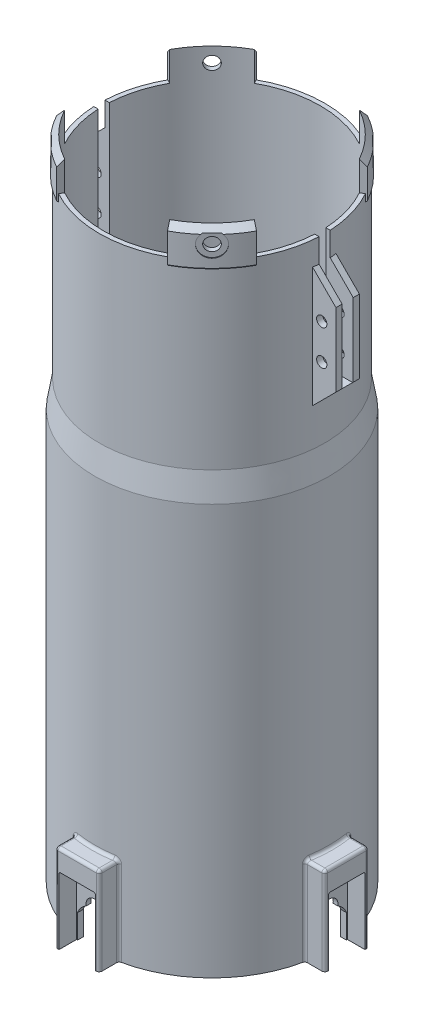
SolidWorks part; units mm, degrees
ref_plane "Front Plane" through (0, 0, 0) normal (0, 0, 1) x (1, 0, 0)
ref_plane "Top Plane" through (0, 0, 0) normal (0, 1, 0) x (1, 0, 0)
ref_plane "Right Plane" through (0, 0, 0) normal (1, 0, 0) x (0, 0, -1)
sketch "Sketch1" plane through (0, 0, 0) normal (0, 1, 0) x (1, 0, 0)
  circle A0 centre (0, 0) radius 40
  circle A1 centre (0, 0) radius 38.5
  dimension "D1" = 80
  dimension "D2" = 1.5
extrude "Boss-Extrude1" add sketch "Sketch1" along normal blind 40
ref_plane "Plane1" through (0, 0, 40) normal (0, 0, 1) x (1, 0, 0)
sketch "Sketch2" plane through (0, 0, 40) normal (0, 0, 1) x (1, 0, 0)
  line L0 (0, 0) -> (0, 45.4693) construction
  line L1 (-40, 0) -> (40, 0) construction
  line L2 (-7.5, 30) -> (7.5, 30)
  line L3 (-7.5, 30) -> (-7.5, 0)
  line L4 (-7.5, 0) -> (7.5, 0)
  line L5 (7.5, 30) -> (7.5, 0)
  line L6 (-7.5, 30) -> (7.5, 0) construction
  line L7 (-7.5, 0) -> (7.5, 30) construction
  point P3 (0, 15)
  dimension "D1" = 15
  dimension "D2" = 30
extrude "Boss-Extrude2" add sketch "Sketch2" along normal blind 6 and the other way up to surface other way up to face at (0, 40, 40)
sketch "Sketch3" plane through (0, 0, 40) normal (0, 0, 1) x (1, 0, 0)
  line L0 (5.8884, 8.095) -> (5.8491, -0.1406)
  line L1 (-5.8884, 8.095) -> (-5.8491, -0.1406)
  line L2 (-5.8491, -0.1406) -> (5.8491, -0.1406)
  arc A18 (-2.9509, 11.5095) -> (-5.8884, 8.095) centre (0, 6) ccw
  arc A19 (2.9509, 11.5095) -> (-2.9509, 11.5095) centre (0, 12.05) ccw
  arc A20 (5.8884, 8.095) -> (2.9509, 11.5095) centre (0, 6) ccw
extrude "Cut-Extrude1" cut sketch "Sketch3" against normal blind 2
sketch "Sketch4" plane through (0, 0, 40) normal (0, 0, 1) x (1, 0, 0)
  line L45 (-5.7, -0.45) -> (5.7, -0.45)
  line L48 (6.2, 0.05) -> (6.2, 22.45)
  line L49 (5.7, 22.95) -> (-5.7, 22.95)
  line L50 (-6.2, 22.45) -> (-6.2, 0.05)
  arc A46 (-6.2, 0.05) -> (-5.7, -0.45) centre (-5.7, 0.05) ccw
  arc A47 (5.7, -0.45) -> (6.2, 0.05) centre (5.7, 0.05) ccw
  arc A48 (6.2, 22.45) -> (5.7, 22.95) centre (5.7, 22.45) ccw
  arc A49 (-5.7, 22.95) -> (-6.2, 22.45) centre (-5.7, 22.45) ccw
extrude "Cut-Extrude2" cut sketch "Sketch4" along normal through all
ref_plane "Plane2" through (0, 0, 41.5) normal (0, 0, 1) x (1, 0, 0)
sketch "Sketch5" plane through (0, 0, 41.5) normal (0, 0, 1) x (1, 0, 0)
  line L66 (-0.3, 25.966) -> (0.3, 25.966)
  line L75 (-5.7, 22.85) -> (-6.2, 22.85)
  line L76 (5.7, 22.85) -> (-5.7, 22.85)
  line L77 (6.2, 22.85) -> (5.7, 22.85)
  line L78 (6.2, 27.05) -> (6.2, 22.85)
  line L79 (0.8, 27.55) -> (5.7, 27.55)
  line L80 (0.3, 25.966) -> (0.3, 27.05)
  line L81 (-0.3, 27.05) -> (-0.3, 25.966)
  line L82 (-5.7, 27.55) -> (-0.8, 27.55)
  line L83 (-6.2, 22.85) -> (-6.2, 27.05)
  arc A42 (6.2, 27.05) -> (5.7, 27.55) centre (5.7, 27.05) ccw
  arc A43 (0.8, 27.55) -> (0.3, 27.05) centre (0.8, 27.05) ccw
  arc A44 (-0.3, 27.05) -> (-0.8, 27.55) centre (-0.8, 27.05) ccw
  arc A45 (-5.7, 27.55) -> (-6.2, 27.05) centre (-5.7, 27.05) ccw
extrude "Cut-Extrude3" cut sketch "Sketch5" along normal blind 3.1
fillet "Fillet1" radius 1 8 edges at (0, 30, 40) (7.5, 30, 42.6453) (7.5, 15, 46) (7.5, 15, 39.2906) (-7.5, 15, 39.2906) (-7.5, 30, 42.6453) (-7.5, 15, 46) (0, 30, 46)
pattern_circular "CirPattern1" count 4 over 360 about axis through (0, 40, 0) along (0, -1, 0) of "Boss-Extrude2", "Cut-Extrude1", "Cut-Extrude2", "Cut-Extrude3", "Fillet1"
sketch "Sketch6" plane through (0, 40, 0) normal (0, 1, 0) x (1, 0, 0)
  circle A0 centre (0, 0) radius 38.5 construction
  circle A1 centre (0, 0) radius 40
  circle A2 centre (0, 0) radius 40
  circle A3 centre (0, 0) radius 38.5
  dimension "D1" = 0
extrude "Boss-Extrude4" add sketch "Sketch6" along normal blind 100
ref_plane "Plane3" through (0, 140, 0) normal (0, 1, 0) x (1, 0, 0)
sketch "Sketch7" plane through (0, 0, 0) normal (0, 0, 1) x (1, 0, 0)
  line L0 (-38.5, 140) -> (-35.194, 160)
  line L1 (38.5, 140) -> (-38.5, 140) construction
  line L2 (-35.194, 160) -> (-37, 160)
  line L3 (-37, 160) -> (-37, 211)
  line L4 (-37, 211) -> (-38.5, 211)
  line L5 (-38.5, 211) -> (-38.5, 149.0744)
  line L6 (0, 140) -> (0, 217.9928) construction
  line L7 (-40, 140) -> (-38.5, 149.0744)
  line L8 (40, 140) -> (-40, 140) construction
  line L9 (-38.5, 140) -> (-40, 140)
  line L10 (40, 140) -> (-40, 140) construction
  point P19 (-36.097, 160)
  dimension "D1" = 1.5
  dimension "D2" = 37
  dimension "D3" = 1.806
  dimension "D4" = 38.5
  dimension "D5" = 1.5
  dimension "D6" = 51
  dimension "D7" = 20
revolve "Revolve1" add sketch "Sketch7" angle 360 about L6
sketch "Sketch8" plane through (0, 0, 0) normal (0, 0, 1) x (1, 0, 0)
  line L0 (-46.3008, 182.5) -> (46.3008, 182.5) construction
  line L2 (-46.3008, 195) -> (-37.5, 203.8008)
  line L3 (-37.5, 211) -> (-37.5, 149.0744)
  line L4 (-37.5, 203.8008) -> (-37.5, 161.1992)
  line L5 (-46.3008, 170) -> (-37.5, 161.1992)
  line L7 (-46.3008, 195) -> (-46.3008, 170)
  circle A0 centre (-41.45, 188.5) radius 1.75
  circle A1 centre (-41.45, 176.5) radius 1.75
  dimension "D2" = 3.5
  dimension "D3" = 3.5
  dimension "D1" = 1
extrude "Boss-Extrude5" add sketch "Sketch8" along normal mid plane 8
sketch "Sketch9" plane through (0, 0, 0) normal (1, 0, 0) x (0, 0, -1)
  line L0 (0, 168.0759) -> (0, 211) construction
  line L1 (38.5, 211) -> (-38.5, 211) construction
  line L7 (-1.9, 195) -> (-1.9, 211)
  line L8 (1.9, 169.8) -> (1.9, 195)
  line L9 (1.9, 169.8) -> (-1.9, 169.8)
  line L10 (-1.9, 169.8) -> (-1.9, 195)
  line L11 (1.9, 195) -> (1.9, 211)
  line L12 (-1.9, 211) -> (1.9, 211)
  point P8 (0, 169.8)
extrude "Cut-Extrude4" cut sketch "Sketch9" against normal through all
mirror "Mirror1" about plane through (0, 0, 0) normal (1, 0, 0) of "Cut-Extrude4", "Boss-Extrude5"
ref_plane "Plane4" through (0, 0, 0) normal (-0.7071, 0, 0.7071) x (0, -1, 0)
sketch "Sketch11" plane through (0, 0, 0) normal (-0.7071, 0, 0.7071) x (0, -1, 0)
  line L0 (-211, 37) -> (-219, 37)
  line L1 (-160, 37) -> (-211, 37) construction
  line L2 (-211, 37) -> (-211, -24.7849) construction
  line L4 (-208.5, 38.5) -> (-211, 38.5)
  line L5 (-219, 39) -> (-209, 39)
  line L6 (-209, 39) -> (-208.5, 38.5)
  line L7 (-149.0744, 38.5) -> (-211, 38.5) construction
  line L8 (-211, 38.5) -> (-211, -25.8469) construction
  line L9 (-211, 38.5) -> (-211, 37)
  line L10 (-219, 37) -> (-221, 37)
  line L11 (-221, 37) -> (-219, 39)
  dimension "D1" = 2
  dimension "D3" = 45
  dimension "D4" = 10
  dimension "D5" = 2.5
revolve "Revolve2" add sketch "Sketch11" angle 32 mid plane about axis through (0, 140, 0) along (0, -1, 0)
ref_plane "Plane5" through (27.5772, 0, 27.5772) normal (0.7071, 0, 0.7071) x (0.7071, 0, -0.7071)
sketch "Sketch12" plane through (27.5772, 0, 27.5772) normal (0.7071, 0, 0.7071) x (0.7071, 0, -0.7071)
  line L0 (0, 209) -> (0, 219) construction
  line L1 (-10.612, 211) -> (-38.5, 211) construction
  circle A0 centre (0, 216) radius 2.25
  dimension "D1" = 4.5
  dimension "D2" = 5
extrude "Cut-Extrude5" cut sketch "Sketch12" against normal blind 8
sketch "Sketch13" plane through (27.5772, 0, 27.5772) normal (0.7071, 0, 0.7071) x (0.7071, 0, -0.7071)
  circle A0 centre (0, 216) radius 4
  dimension "D1" = 8
extrude "Cut-Extrude6" cut sketch "Sketch13" against normal blind 0.3
pattern_circular "CirPattern2" count 4 over 360 about axis through (0, 211, 0) along (0, 1, 0) of "Revolve2", "Cut-Extrude5", "Cut-Extrude6" reverse direction yes
